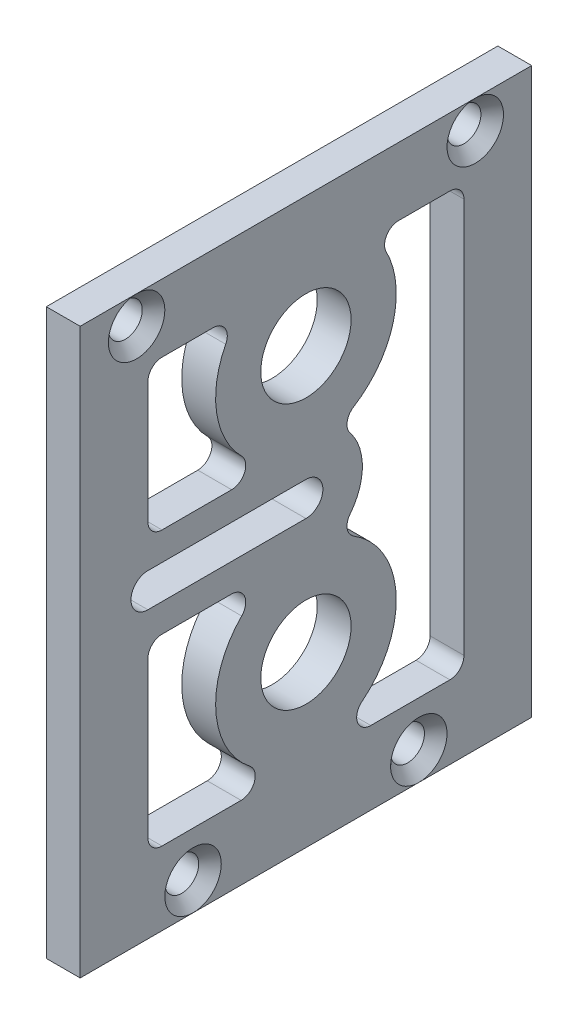
SolidWorks part; units mm, degrees
ref_plane "Plan de face" through (0, 0, 0) normal (0, 0, 1) x (1, 0, 0)
ref_plane "Plan de dessus" through (0, 0, 0) normal (0, 1, 0) x (1, 0, 0)
ref_plane "Plan de droite" through (0, 0, 0) normal (1, 0, 0) x (0, 0, -1)
sketch "Esquisse1" plane through (0, 0, 0) normal (1, 0, 0) x (0, 0, -1)
  line L1 (0, 0) -> (80, 0)
  line L2 (0, 0) -> (0, 100)
  line L3 (0, 100) -> (80, 100)
  line L4 (80, 0) -> (80, 100)
  dimension "D1" = 100
  dimension "D2" = 80
extrude "Extrusion1" add sketch "Esquisse1" along normal blind 6
sketch "Esquisse2" plane through (6, 0, 0) normal (1, 0, 0) x (0, 0, -1)
  line L0 (80, 0) -> (80, 100) construction
  line L1 (80, 100) -> (0, 100) construction
  circle A0 centre (40, 77) radius 8
  circle A1 centre (40, 30) radius 8
  dimension "D1" = 16
  dimension "D2" = 40
  dimension "D3" = 23
sketch "Esquisse3" plane through (6, 0, 0) normal (1, 0, 0) x (0, 0, -1)
  line L0 (0, 100) -> (0, 0) construction
  line L1 (80, 100) -> (0, 100) construction
  line L3 (0, 0) -> (80, 0) construction
  circle A0 centre (10, 95) radius 3
  circle A2 centre (70, 95) radius 3
  circle A3 centre (20, 5) radius 3
  circle A4 centre (60, 5) radius 3
  dimension "D1" = 6
  dimension "D2" = 10
  dimension "D3" = 5
  dimension "D4" = 6
  dimension "D6" = 5
  dimension "D5" = 20
sketch "Esquisse4" plane through (6, 0, 0) normal (1, 0, 0) x (0, 0, -1)
  line L0 (0, 100) -> (0, 0) construction
  line L1 (14.5, 88) -> (23.5683, 88)
  line L2 (12, 85.5) -> (12, 64)
  line L3 (14.5, 61.5) -> (26.8376, 61.5)
  line L4 (0, 0) -> (80, 0) construction
  line L5 (80, 100) -> (0, 100) construction
  line L6 (12, 56.5) -> (40, 56.5)
  line L7 (14.5, 45.5) -> (26.8376, 45.5)
  line L8 (12, 50.5) -> (40, 50.5)
  line L9 (12, 43) -> (12, 15.5)
  line L10 (14.5, 13) -> (28.5109, 13)
  line L11 (80, 0) -> (80, 100) construction
  line L12 (65.5, 13) -> (51.4891, 13)
  line L13 (68, 15.5) -> (68, 85.5)
  line L14 (65.5, 88) -> (56.4317, 88)
  arc A0 (25.7888, 84.3514) -> (28.6163, 65.7568) centre (40, 77) ccw
  arc A1 (14.5, 88) -> (12, 85.5) centre (14.5, 85.5) ccw
  arc A2 (12, 64) -> (14.5, 61.5) centre (14.5, 64) ccw
  arc A3 (26.8376, 61.5) -> (28.6163, 65.7568) centre (26.8376, 64) ccw
  arc A4 (25.7888, 84.3514) -> (23.5683, 88) centre (23.5683, 85.5) ccw
  arc A5 (12, 56.5) -> (12, 50.5) centre (12, 53.5) ccw
  arc A6 (40, 50.5) -> (40, 56.5) centre (40, 53.5) ccw
  arc A7 (28.6163, 41.2432) -> (30.0635, 17.4595) centre (40, 30) ccw
  arc A8 (14.5, 45.5) -> (12, 43) centre (14.5, 43) ccw
  arc A9 (28.6163, 41.2432) -> (26.8376, 45.5) centre (26.8376, 43) ccw
  arc A10 (12, 15.5) -> (14.5, 13) centre (14.5, 15.5) ccw
  arc A11 (28.5109, 13) -> (30.0635, 17.4595) centre (28.5109, 15.5) ccw
  arc A14 (49.9365, 17.4595) -> (48.453, 43.5848) centre (40, 30) ccw
  arc A15 (56.4317, 88) -> (54.2112, 84.3514) centre (56.4317, 85.5) ccw
  arc A16 (68, 85.5) -> (65.5, 88) centre (65.5, 85.5) ccw
  arc A17 (48.453, 63.4152) -> (47.819, 59.734) centre (49.7737, 61.2926) ccw
  arc A18 (47.819, 47.266) -> (48.453, 43.5848) centre (49.7737, 45.7074) ccw
  arc A19 (49.9365, 17.4595) -> (51.4891, 13) centre (51.4891, 15.5) ccw
  arc A20 (65.5, 13) -> (68, 15.5) centre (65.5, 15.5) ccw
  arc A22 (48.453, 63.4152) -> (54.2112, 84.3514) centre (40, 77) ccw
  arc A23 (47.819, 47.266) -> (47.819, 59.734) centre (40, 53.5) ccw
  dimension "D4" = 32
  dimension "D5" = 5
  dimension "D6" = 5
  dimension "D7" = 5
  dimension "D8" = 5
  dimension "D14" = 32
  dimension "D15" = 5
  dimension "D16" = 5
  dimension "D17" = 5
  dimension "D18" = 5
  dimension "D22" = 5
  dimension "D23" = 5
  dimension "D24" = 5
  dimension "D25" = 5
  dimension "D26" = 5
  dimension "D27" = 5
  dimension "D1" = 12
  dimension "D2" = 12
  dimension "D3" = 6
  dimension "D9" = 5
  dimension "D10" = 28
  dimension "D11" = 12
  dimension "D12" = 5
  dimension "D13" = 13
  dimension "D19" = 13
  dimension "D20" = 12
  dimension "D21" = 12
extrude "Extrusion3" cut sketch "Esquisse2" against normal through all
extrude "Extrusion4" cut sketch "Esquisse3" against normal through all
extrude "Extrusion5" cut sketch "Esquisse4" against normal through all
chamfer "Chanfrein1" distance 2 angle 45 4 edges at (6, 5, -23) (6, 5, -57) (6, 95, -67) (6, 95, -13)
